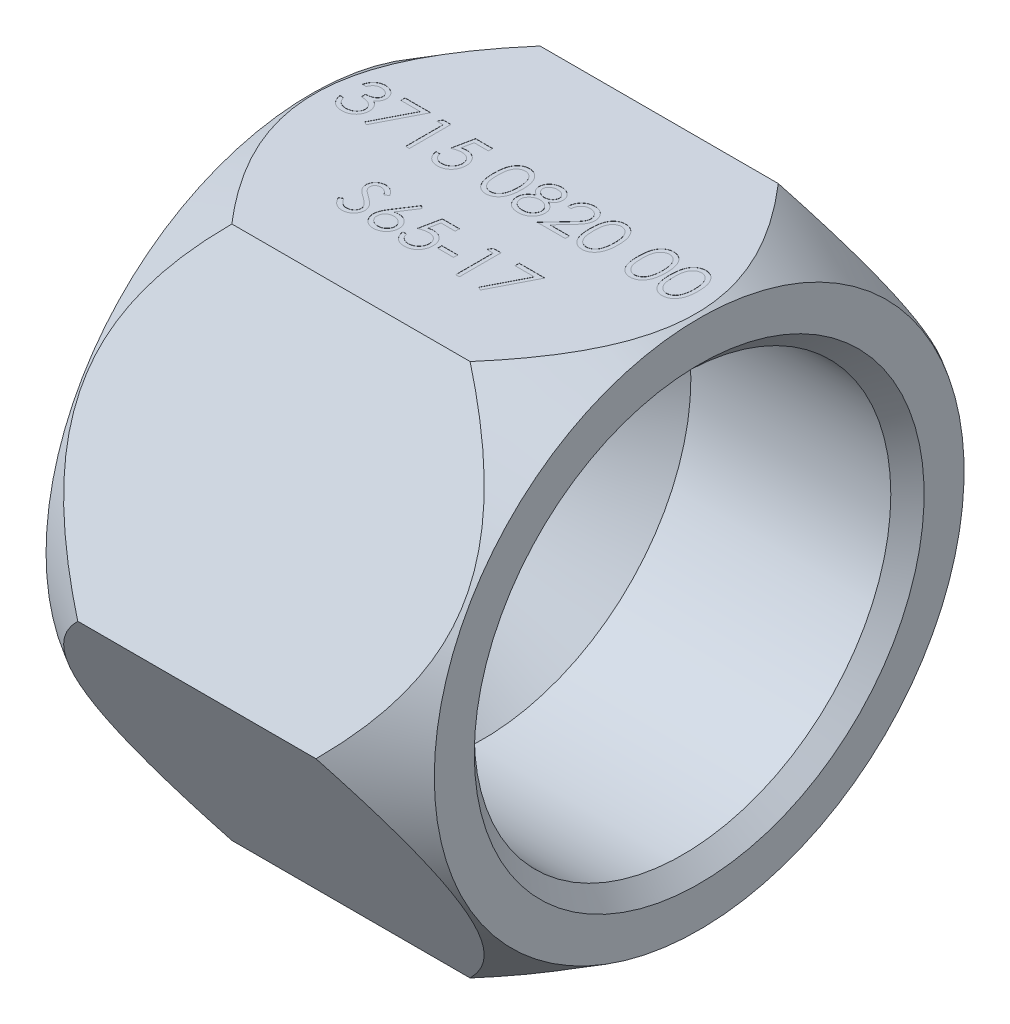
SolidWorks part; units mm, degrees
material "Plain Carbon Steel"
ref_plane "Front Plane" through (0, 0, 0) normal (0, 0, 1) x (1, 0, 0)
ref_plane "Top Plane" through (0, 0, 0) normal (0, 1, 0) x (1, 0, 0)
ref_plane "Right Plane" through (0, 0, 0) normal (1, 0, 0) x (0, 0, -1)
sketch "Sketch1" plane through (0, 0, 0) normal (0, 0, 1) x (1, 0, 0)
  line L0 (0, 0) -> (82.389, 0) construction
  line L1 (0, 0) -> (0, 15.9)
  line L2 (0, 15.9) -> (4.5, 18.5)
  line L3 (4.5, 18.5) -> (18.8, 18.5)
  line L4 (18.8, 18.5) -> (23.3, 15.9)
  line L5 (23.3, 15.9) -> (23.3, 12.5)
  line L6 (23.3, 12.5) -> (10.3, 12.5)
  line L7 (10.3, 12.5) -> (3.3, 7.2251)
  line L8 (3.3, 7.2251) -> (3.3, 0)
  line L9 (0, 0) -> (3.3, 0)
  dimension "D1" = 37
  dimension "D2" = 20
  dimension "D3" = 31.8
  dimension "D5" = 37
  dimension "D7" = 4.5
  dimension "D6" = 4.5
  dimension "D8" = 25
  dimension "D9" = 13
  dimension "D10" = 23.3
  dimension "D11" = 31.8
revolve "Revolve1" add sketch "Sketch1" angle 360 about L0
cosmetic thread "Cosmetic Thread1" parameters "D1"=10, "D2"=27
sketch "Sketch2" plane through (23.3, 0, 0) normal (1, 0, 0) x (0, 0, -1)
  line L1 (9.25, 16.0215) -> (-9.25, 16.0215)
  line L2 (-9.25, 16.0215) -> (-18.5, 0)
  line L3 (-18.5, 0) -> (-9.25, -16.0215)
  line L4 (-9.25, -16.0215) -> (9.25, -16.0215)
  line L5 (9.25, -16.0215) -> (18.5, 0)
  line L6 (18.5, 0) -> (9.25, 16.0215)
  circle A0 centre (0, 0) radius 16.0215 construction
  circle A1 centre (0, 0) radius 18.5 construction
extrude "Extrude1" cut sketch "Sketch2" against normal up to surface (23.3 mm away) flip side to cut up to face at (0, 0, 15.9)
chamfer "Chamfer1" distance 1 angle 45 1 edges at (23.3, 0, 12.5)
sketch "Sketch3" plane through (0, 16.0215, 0) normal (0, 1, 0) x (1, 0, 0)
  line L0 (0, 0) -> (23.0898, 0) construction
  spline S0 degree 3 poles (18.8, -9.25) (19.3656, -8.5964) (19.9119, -7.9133) (20.9163, -6.4987) (21.376, -5.7662) (21.9709, -4.6117) (22.1533, -4.2174) (22.4785, -3.4055) (22.6198, -2.9909) (22.8495, -2.1537) (22.9386, -1.7294) (23.059, -0.8684) (23.0901, -0.4281) (23.089, 0.8806) (22.9644, 1.7376) (22.616, 3.0032) (22.474, 3.4175) (22.1509, 4.2225) (21.9692, 4.6152) (21.5726, 5.3844) (21.3577, 5.7609) (20.9003, 6.5003) (20.6571, 6.8642) (19.9018, 7.9266) (19.3626, 8.5999) (18.8, 9.25) knots 0 0 0 0 0.125 0.125 0.25 0.25 0.3125 0.3125 0.375 0.375 0.4375 0.4375 0.5 0.5 0.625 0.625 0.6875 0.6875 0.75 0.75 0.8125 0.8125 0.875 0.875 1 1 1 1 construction
  text T0 "3715 0820 00\r\nS65-17"
extrude "Cut-Extrude1" cut sketch "Sketch3" against normal blind 0.01
